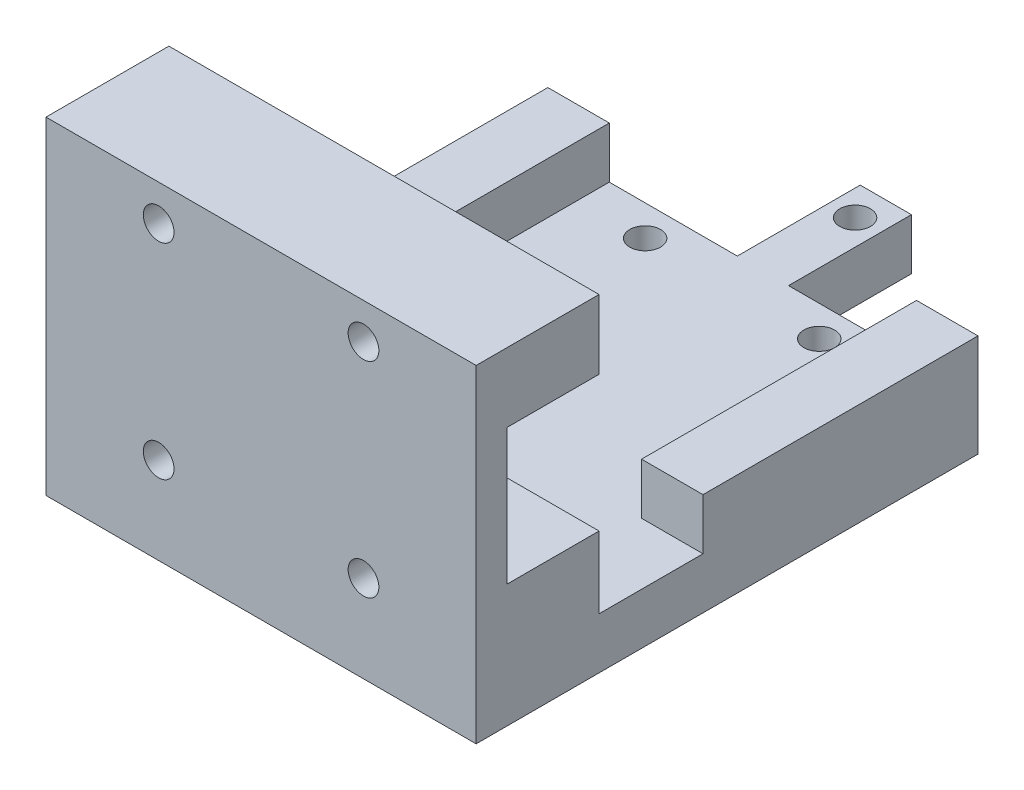
SolidWorks part; units mm, degrees
note: The reader was unsure of these and kept them because the rebuilt part matched: shared geometry of "Sketch2<3>", "Sketch1<3>".
ref_plane "Front Plane" through (0, 0, 0) normal (0, 0, 1) x (1, 0, 0)
ref_plane "Top Plane" through (0, 0, 0) normal (0, 1, 0) x (1, 0, 0)
ref_plane "Right Plane" through (0, 0, 0) normal (1, 0, 0) x (0, 0, -1)
sketch "Sketch1" plane through (0, 0, 0) normal (0, 0, 1) x (1, 0, 0)
  line L0 (16, -13.5) -> (-16, -13.5) construction
  line L1 (21, -6.5) -> (-21, -6.5)
  line L2 (21, -6.5) -> (21, -13.5)
  line L3 (21, -13.5) -> (-21, -13.5)
  line L4 (-21, -6.5) -> (-21, -13.5)
  line L5 (21, 6.75) -> (-21, 6.75)
  line L6 (21, 6.75) -> (21, 13.5)
  line L7 (21, 13.5) -> (-21, 13.5)
  line L8 (-21, 6.75) -> (-21, 13.5)
  line L9 (-21, 6.75) -> (21, 6.75)
  line L10 (-21, 6.75) -> (-21, -6.5)
  line L11 (-21, -6.5) -> (21, -6.5)
  line L12 (21, 6.75) -> (21, -6.5)
  line L14 (-16, 13.5) -> (16, 13.5) construction
  line L15 (-21, -13) -> (-21, 13) construction
  line L16 (21, 13) -> (21, -13) construction
  circle A0 centre (10, -10) radius 1.5
  circle A1 centre (-10, -10) radius 1.5
  circle A2 centre (-10, 10) radius 1.5
  circle A3 centre (10, 10) radius 1.5
  dimension "D1" = 3
  dimension "D2" = 3
  dimension "D3" = 3
  dimension "D4" = 3
  dimension "D5" = 0
  dimension "D6" = 0
  dimension "D7" = 0
  dimension "D8" = 0
extrude "Boss-Extrude1" add sketch "Sketch1" along normal blind 12 contours L1 L4 L3 L2 A1 A0 | L8 L5 L6 L7 A3 A2
sketch "Sketch2" plane through (0, -13.5, 0) normal (0, -1, 0) x (1, 0, 0)
  line L1 (21, 12) -> (-21, 12)
  line L2 (21, 12) -> (21, -37)
  line L3 (21, -37) -> (-21, -37)
  line L4 (-21, 12) -> (-21, -37)
  line L5 (-21, -9.5) -> (-21, -0.5) construction
  line L6 (2.5, -37) -> (2.5, -49)
  line L7 (-15, -49) -> (15, -49) construction
  line L8 (2.5, -49) -> (-2.5, -49)
  line L9 (-2.5, -49) -> (-2.5, -37)
  line L10 (15, -49) -> (15, -31) construction
  line L11 (21, -37) -> (15, -37)
  line L12 (21, -37) -> (21, -10.15)
  line L13 (21, -10.15) -> (15, -10.15)
  line L14 (15, -37) -> (15, -10.15)
  line L15 (21, -10) -> (16, -10) construction
  line L16 (-15, -49) -> (-15, -31) construction
  line L17 (-21, -37) -> (-15, -37)
  line L18 (-21, -37) -> (-21, -10.15)
  line L19 (-21, -10.15) -> (-15, -10.15)
  line L20 (-15, -37) -> (-15, -10.15)
  line L26 (-21, -37) -> (-15, -37)
  line L32 (21, -37) -> (15, -37)
  line L34 (0, -37) -> (0, -49) construction
  line L35 (0, -49) -> (0, -64) construction
  circle A0 centre (8.5, -34) radius 1.25 construction
  circle A1 centre (9, -43) radius 5.5
  circle A2 centre (-9, -43) radius 5.5
  circle A3 centre (0, -56.5) radius 4
  circle A4 centre (0, -46) radius 1.25 construction
  circle A5 centre (0, -46) radius 1.5
  circle A6 centre (8.5, -34) radius 1.5
  circle A7 centre (-8.5, -34) radius 1.5
  dimension "D2" = 3
  dimension "D3" = 11
  dimension "D4" = 11
  dimension "D5" = 2.5
  dimension "D6" = 2.5
  dimension "D11" = 3
  dimension "D12" = 3
  dimension "D13" = 3
  dimension "D16" = 8
  dimension "D1" = 0
  dimension "D7" = 0
  dimension "D8" = 0.15
  dimension "D9" = 0
  dimension "D10" = 0
extrude "Boss-Extrude2" add sketch "Sketch2" along normal blind 5
extrude "Boss-Extrude3" add sketch "Sketch2<3>" against normal blind 5
sketch "Sketch2<3>" plane through (0, -13.5, 0) normal (0, -1, 0) x (1, 0, 0) same geometry as "Sketch2"
extrude "Boss-Extrude4" add sketch "Sketch1<3>" against normal blind 3 from surface at 12 contours L12 L5 L10 L1 starting at face at (-8.5, -10, 12)
sketch "Sketch1<3>" plane through (0, 0, 0) normal (0, 0, 1) x (1, 0, 0) same geometry as "Sketch1"
